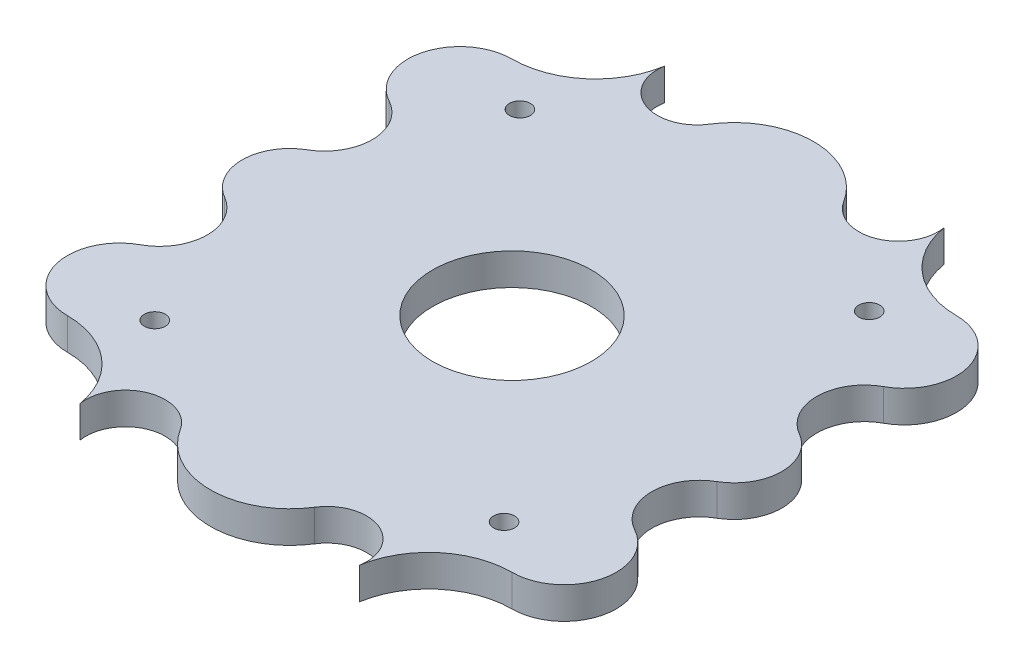
SolidWorks part; units mm, degrees
ref_plane "Alzado" through (0, 0, 0) normal (0, 0, 1) x (1, 0, 0)
ref_plane "Planta" through (0, 0, 0) normal (0, 1, 0) x (1, 0, 0)
ref_plane "Vista lateral" through (0, 0, 0) normal (1, 0, 0) x (0, 0, -1)
sketch "Croquis1" plane through (0, 0, 0) normal (0, 1, 0) x (1, 0, 0)
  line L0 (0, 138.5041) -> (0, -177.2184) construction
  line L2 (-70, -70) -> (-70, 70)
  line L4 (70, -70) -> (70, 70)
  line L5 (-70, -70) -> (70, 70) construction
  line L6 (-70, 70) -> (70, -70) construction
  line L7 (-103.4324, 0) -> (144.2109, 0) construction
  arc A1 (-21.1476, -83.3333) -> (21.1476, -83.3333) centre (0, -70) ccw
  arc A5 (-21.1476, -83.3333) -> (-44.0559, -92.0276) centre (-31.7214, -90) ccw
  arc A6 (-44.0559, -92.0276) -> (-70, -70) centre (-70, -96.2923) ccw
  arc A7 (21.1476, -83.3333) -> (44.0559, -92.0276) centre (31.7214, -90) cw
  arc A8 (44.0559, -92.0276) -> (70, -70) centre (70, -96.2923) cw
  arc A9 (44.0559, 92.0276) -> (70, 70) centre (70, 96.2923) ccw
  arc A10 (21.1476, 83.3333) -> (44.0559, 92.0276) centre (31.7214, 90) ccw
  arc A11 (-21.1476, 83.3333) -> (21.1476, 83.3333) centre (0, 70) cw
  arc A12 (-21.1476, 83.3333) -> (-44.0559, 92.0276) centre (-31.7214, 90) cw
  arc A13 (-44.0559, 92.0276) -> (-70, 70) centre (-70, 96.2923) cw
  point P0 (0, 0)
  point P14 (-25, -70)
  point P16 (-70, -70)
  dimension "D4" = 50
  dimension "D6" = 25
  dimension "D1" = 140
  dimension "D2" = 140
extrude "Saliente-Extruir1" add sketch "Croquis1" along normal blind 10
sketch "Croquis2" plane through (0, 10, 0) normal (0, 1, 0) x (1, 0, 0)
  line L0 (70, -70) -> (70, 70) construction
  line L1 (70, 70) -> (70, -70)
  line L2 (0, 152.4123) -> (0, -148.5895) construction
  line L3 (-96.3545, 0) -> (168.0513, 0) construction
  line L4 (-70, 70) -> (-70, -70)
  arc A0 (77.5, -12.9904) -> (77.5, 12.9904) centre (70, 0) ccw
  arc A1 (77.838, 39.1605) -> (77.5, 12.9904) centre (85, 25.9808) ccw
  arc A2 (77.838, 39.1605) -> (70, 70) centre (70, 53.5842) ccw
  arc A3 (77.838, -39.1605) -> (77.5, -12.9904) centre (85, -25.9808) cw
  arc A4 (77.838, -39.1605) -> (70, -70) centre (70, -53.5842) cw
  arc A5 (-77.838, -39.1605) -> (-70, -70) centre (-70, -53.5842) ccw
  arc A6 (-77.838, -39.1605) -> (-77.5, -12.9904) centre (-85, -25.9808) ccw
  arc A7 (-77.5, -12.9904) -> (-77.5, 12.9904) centre (-70, 0) cw
  arc A8 (-77.838, 39.1605) -> (-77.5, 12.9904) centre (-85, 25.9808) cw
  arc A9 (-77.838, 39.1605) -> (-70, 70) centre (-70, 53.5842) cw
  line M11 (-70, 70) -> (-70, -70)
  line M17 (70, -70) -> (70, 70)
  dimension "D1" = 30
  dimension "D2" = 30
extrude "Saliente-Extruir2" add sketch "Croquis2" against normal blind 10 contours A9 A8 M11 | A1 A2 L1 | L1 A3 A0 A1 | L4 A8 A7 A6 | A6 A5 L4 | A4 A3 M17 region at (76.7408, 10, -52.7676) region at (76.7408, 10, 52.7676) region at (75.931, 10, 0) region at (-76.7408, 10, 52.7676) region at (-75.931, 10, 0) region at (-76.7408, 10, -52.7676)
sketch "Croquis3" plane through (0, 10, 0) normal (0, 1, 0) x (1, 0, 0)
  circle A0 centre (0, 0) radius 25
  dimension "D1" = 50
extrude "Cortar-Extruir1" cut sketch "Croquis3" against normal blind 10
hole_wizard "Refrentado para tornillo con cabeza hueca de M61" positions "Croquis3D1" profile "Croquis4" counterbore size "M6" standard "DIN" end condition through all
sketch3d "Croquis3D1"
  line L1 (55, 0, -57.5) -> (55, 0, 57.5) construction
  line L2 (55, 0, -57.5) -> (-55, 0, -57.5) construction
  line L3 (-55, 0, -57.5) -> (-55, 0, 57.5) construction
  line L4 (55, 0, 57.5) -> (-55, 0, 57.5) construction
  line L5 (55, 0, -57.5) -> (-55, 0, 57.5) construction
  line L6 (-55, 0, -57.5) -> (55, 0, 57.5) construction
  point P0 (-55, 0, 57.5)
  point P2 (55, 0, 57.5)
  point P4 (55, 0, -57.5)
  point P6 (-55, 0, -57.5)
  point P9 (0, 0, 0)
  point P72 (0, 0, 0)
  point P73 (0, 0, 0)
  point P74 (0, 0, 0)
  dimension "D1" = 115
  dimension "D2" = 110
sketch "Croquis4" plane through (-55, 0, 57.5) normal (1, 0, 0) x (0, 0, -1)
  line L0 (0, 0) -> (0, 10)
  line L1 (0, 10) -> (3.3, 10)
  line L3 (3.3, 10) -> (3.3, 4.4)
  line L4 (3.3, 4.4) -> (5.5, 4.4)
  line L5 (5.5, 4.4) -> (5.5, 0)
  line L7 (5.5, 0) -> (0, 0)
  line L11 (0, -6.35) -> (0, 107.95) construction
  dimension "Diámetro de taladro hasta el siguiente" = 6.6
  dimension "Profundidad de taladro hasta el siguiente" = 10
  dimension "Diámetro de refrentado" = 11
  dimension "Profundidad de refrentado" = 4.4
